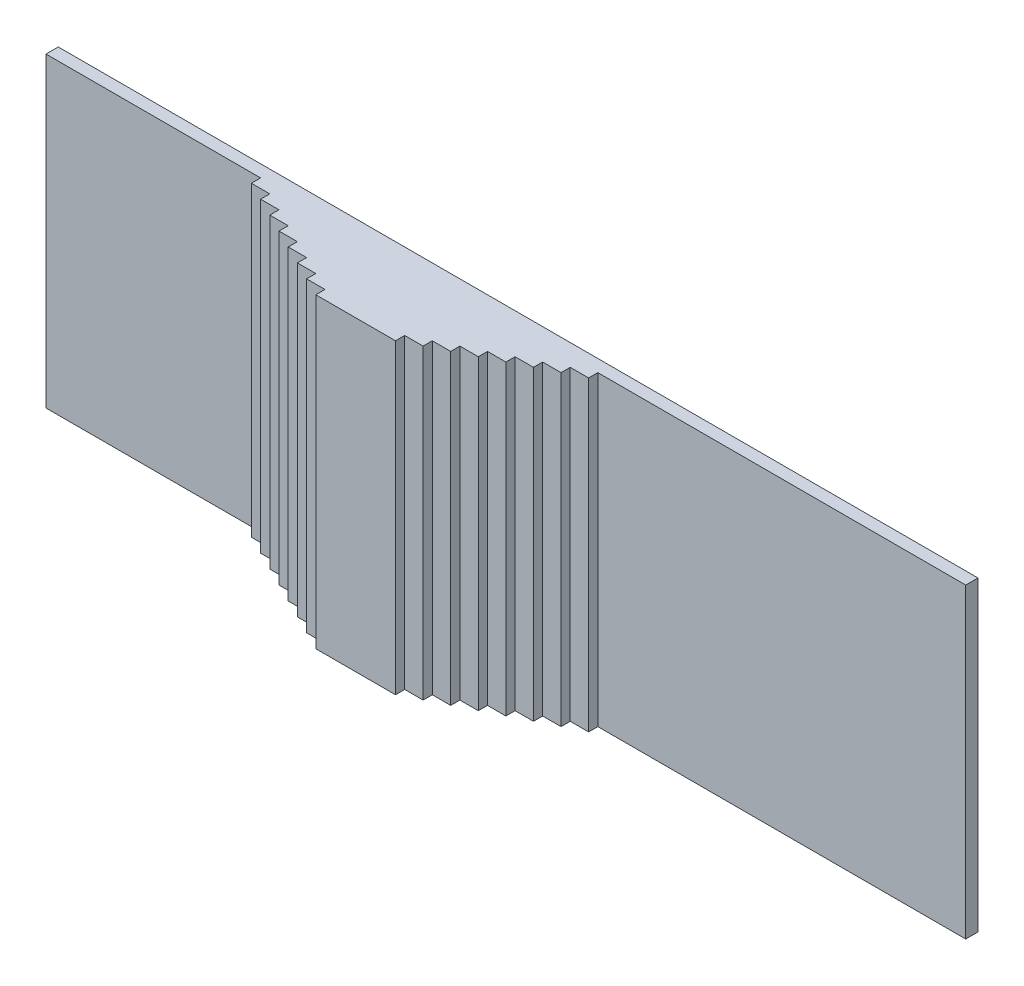
SolidWorks part; units mm, degrees
note: The reader was unsure of these and kept them because the rebuilt part matched: shared geometry of "Sketch4<4>", "Sketch4<5>", "Sketch4<6>", "Sketch4<7>", "Sketch4<8>", "Sketch4<9>", "Sketch4<10>", "Sketch10<3>", "Sketch10<4>", "Sketch10<5>", "Sketch10<6>", "Sketch10<7>", "Sketch10<8>".
ref_plane "Front Plane" through (0, 0, 0) normal (0, 0, 1) x (1, 0, 0)
ref_plane "Top Plane" through (0, 0, 0) normal (0, 1, 0) x (1, 0, 0)
ref_plane "Right Plane" through (0, 0, 0) normal (1, 0, 0) x (0, 0, -1)
sketch "Sketch3" plane through (0, 0, 0) normal (0, 0, 1) x (1, 0, 0)
  line L1 (-2500, 2500) -> (12500, 2500)
  line L2 (-2500, 2500) -> (-2500, -2500)
  line L3 (-2500, -2500) -> (12500, -2500)
  line L4 (12500, 2500) -> (12500, -2500)
  line L5 (-2500, 2500) -> (12500, -2500) construction
  line L6 (-2500, -2500) -> (12500, 2500) construction
  point P0 (5000, 0)
  dimension "D1" = 15000
  dimension "D2" = 5000
  dimension "D3" = 5000
extrude "Boss-Extrude1" add sketch "Sketch3" along normal blind 200
sketch "Sketch4" plane through (0, 0, 200) normal (0, 0, 1) x (1, 0, 0)
  line L0 (-2500, -2500) -> (12500, -2500) construction
  line L1 (1000, -2500) -> (1300, -2500)
  line L2 (1000, -2500) -> (1000, 2500)
  line L3 (1000, 2500) -> (1300, 2500)
  line L4 (1300, -2500) -> (1300, 2500)
  line L5 (12500, 2500) -> (-2500, 2500) construction
  line L6 (1300, -2500) -> (1300, 2500)
  line L7 (1300, -2500) -> (1600, -2500)
  line L8 (1600, -2500) -> (1600, 2500)
  line L9 (1300, 2500) -> (1600, 2500)
  line L10 (1600, -2500) -> (1600, 2500)
  line L11 (1600, -2500) -> (1900, -2500)
  line L12 (1900, -2500) -> (1900, 2500)
  line L13 (1600, 2500) -> (1900, 2500)
  line L14 (1900, -2500) -> (1900, 2500)
  line L15 (1900, -2500) -> (2200, -2500)
  line L16 (2200, -2500) -> (2200, 2500)
  line L17 (1900, 2500) -> (2200, 2500)
  line L18 (2200, -2500) -> (2200, 2500)
  line L19 (2200, -2500) -> (2500, -2500)
  line L20 (2500, -2500) -> (2500, 2500)
  line L21 (2200, 2500) -> (2500, 2500)
  line L22 (2500, -2500) -> (2500, 2500)
  line L23 (2500, -2500) -> (2800, -2500)
  line L24 (2800, -2500) -> (2800, 2500)
  line L25 (2500, 2500) -> (2800, 2500)
  line L26 (2800, -2500) -> (2800, 2500)
  line L27 (2800, -2500) -> (3100, -2500)
  line L28 (3100, -2500) -> (3100, 2500)
  line L29 (2800, 2500) -> (3100, 2500)
  line L30 (3100, -2500) -> (3100, 2500)
  line L31 (3100, -2500) -> (3400, -2500)
  line L32 (3400, -2500) -> (3400, 2500)
  line L33 (3100, 2500) -> (3400, 2500)
  line M6 (12500, 2500) -> (-2500, 2500)
  line M8 (-2500, -2500) -> (12500, -2500)
  dimension "D1" = 1000
  dimension "D2" = 300
  dimension "D3" = 8
extrude "Step1" add sketch "Sketch4" along normal blind 150 contours L4 L2 M8 M6
extrude "Step2" add sketch "Sketch4<4>" along normal blind 300 contours L8 L4 M8 M6
sketch "Sketch4<4>" plane through (0, 0, 200) normal (0, 0, 1) x (1, 0, 0) same geometry as "Sketch4"
extrude "Step3" add sketch "Sketch4<5>" along normal blind 450 contours L12 L8 M8 M6
sketch "Sketch4<5>" plane through (0, 0, 200) normal (0, 0, 1) x (1, 0, 0) same geometry as "Sketch4"
extrude "Step4" add sketch "Sketch4<6>" along normal blind 600 contours L16 L12 M8 M6
sketch "Sketch4<6>" plane through (0, 0, 200) normal (0, 0, 1) x (1, 0, 0) same geometry as "Sketch4"
extrude "Step5" add sketch "Sketch4<7>" along normal blind 750 contours L20 L16 M8 M6
sketch "Sketch4<7>" plane through (0, 0, 200) normal (0, 0, 1) x (1, 0, 0) same geometry as "Sketch4"
extrude "Step6" add sketch "Sketch4<8>" along normal blind 900 contours L24 L20 M8 M6
sketch "Sketch4<8>" plane through (0, 0, 200) normal (0, 0, 1) x (1, 0, 0) same geometry as "Sketch4"
extrude "Step7" add sketch "Sketch4<9>" along normal blind 1050 contours L28 L24 M8 M6
sketch "Sketch4<9>" plane through (0, 0, 200) normal (0, 0, 1) x (1, 0, 0) same geometry as "Sketch4"
extrude "Step8" add sketch "Sketch4<10>" along normal blind 1200 contours L32 L28 M8 M6
sketch "Sketch4<10>" plane through (0, 0, 200) normal (0, 0, 1) x (1, 0, 0) same geometry as "Sketch4"
sketch "Sketch8" plane through (0, 0, 200) normal (0, 0, 1) x (1, 0, 0)
  line L4 (12500, 2500) -> (3400, 2500)
  line L5 (3400, 2500) -> (3400, -2500)
  line L6 (3400, -2500) -> (12500, -2500)
  line L7 (12500, -2500) -> (12500, 2500)
  line L8 (12500, 2500) -> (3400, 2500)
  line L10 (3400, -2500) -> (12500, -2500)
  line L11 (12500, -2500) -> (12500, 2500)
  line L12 (3400, 2500) -> (3400, -2500)
  dimension "D1" = 0
sketch "Sketch9" plane through (0, 0, 200) normal (0, 0, 1) x (1, 0, 0)
  line L0 (4400, -2500) -> (4400, 2500)
  line L4 (12500, 2500) -> (3400, 2500)
  line L5 (3400, 2500) -> (3400, -2500)
  line L6 (3400, -2500) -> (12500, -2500)
  line L7 (12500, -2500) -> (12500, 2500)
  line L8 (12500, 2500) -> (3400, 2500)
  line L9 (3400, 2500) -> (3400, -2500)
  line L10 (3400, -2500) -> (12500, -2500)
  line L11 (12500, -2500) -> (12500, 2500)
  line M6 (12500, 2500) -> (3400, 2500)
  line M7 (3400, 2500) -> (3400, -2500)
  line M8 (3400, -2500) -> (12500, -2500)
  dimension "D2" = 1000
  dimension "D1" = 0
extrude "Boss-Extrude2" add sketch "Sketch9" along normal blind 1200 contours L0 M8 M6 M7
sketch "Sketch10" plane through (0, 0, 200) normal (0, 0, 1) x (1, 0, 0)
  line L0 (4700, -2500) -> (4700, 2500)
  line L1 (4400, -2500) -> (4700, -2500)
  line L2 (4400, -2500) -> (4400, 2500)
  line L3 (4400, 2500) -> (4700, 2500)
  line L4 (12500, 2500) -> (4400, 2500)
  line L5 (4400, 2500) -> (4400, -2500)
  line L6 (4400, -2500) -> (12500, -2500)
  line L7 (12500, -2500) -> (12500, 2500)
  line L8 (12500, 2500) -> (4400, 2500)
  line L9 (4400, 2500) -> (4400, -2500)
  line L10 (4400, -2500) -> (12500, -2500)
  line L11 (12500, -2500) -> (12500, 2500)
  line L12 (4700, -2500) -> (4700, 2500)
  line L13 (4700, -2500) -> (5000, -2500)
  line L14 (5000, -2500) -> (5000, 2500)
  line L15 (4700, 2500) -> (5000, 2500)
  line L16 (5000, -2500) -> (5000, 2500)
  line L17 (5000, -2500) -> (5300, -2500)
  line L18 (5300, -2500) -> (5300, 2500)
  line L19 (5000, 2500) -> (5300, 2500)
  line L20 (5300, -2500) -> (5300, 2500)
  line L21 (5300, -2500) -> (5600, -2500)
  line L22 (5600, -2500) -> (5600, 2500)
  line L23 (5300, 2500) -> (5600, 2500)
  line L24 (5600, -2500) -> (5600, 2500)
  line L25 (5600, -2500) -> (5900, -2500)
  line L26 (5900, -2500) -> (5900, 2500)
  line L27 (5600, 2500) -> (5900, 2500)
  line L28 (5900, -2500) -> (5900, 2500)
  line L29 (5900, -2500) -> (6200, -2500)
  line L30 (6200, -2500) -> (6200, 2500)
  line L31 (5900, 2500) -> (6200, 2500)
  line L32 (6200, -2500) -> (6200, 2500)
  line L33 (6200, -2500) -> (6500, -2500)
  line L34 (6500, -2500) -> (6500, 2500)
  line L35 (6200, 2500) -> (6500, 2500)
  line L36 (6500, -2500) -> (6500, 2500)
  line L37 (6500, -2500) -> (6800, -2500)
  line L38 (6800, -2500) -> (6800, 2500)
  line L39 (6500, 2500) -> (6800, 2500)
  dimension "D2" = 300
  dimension "D1" = 0
  dimension "D3" = 8
extrude "Boss-Extrude3" add sketch "Sketch10" along normal blind 1050 contours L22 L0 L20 L21
extrude "Boss-Extrude4" add sketch "Sketch10<3>" along normal blind 900 contours L22 L14 L8 L0
sketch "Sketch10<3>" plane through (0, 0, 200) normal (0, 0, 1) x (1, 0, 0) same geometry as "Sketch10"
extrude "Boss-Extrude5" add sketch "Sketch10<4>" along normal blind 750 contours L10 L18 L8 L14
sketch "Sketch10<4>" plane through (0, 0, 200) normal (0, 0, 1) x (1, 0, 0) same geometry as "Sketch10"
extrude "Boss-Extrude6" add sketch "Sketch10<5>" along normal blind 600 contours L22 L8 L18
sketch "Sketch10<5>" plane through (0, 0, 200) normal (0, 0, 1) x (1, 0, 0) same geometry as "Sketch10"
extrude "Boss-Extrude7" add sketch "Sketch10<6>" along normal blind 450 contours L10 L26 L8 L22
sketch "Sketch10<6>" plane through (0, 0, 200) normal (0, 0, 1) x (1, 0, 0) same geometry as "Sketch10"
extrude "Boss-Extrude8" add sketch "Sketch10<7>" along normal blind 300 contours L22 L30 L8 L26
sketch "Sketch10<7>" plane through (0, 0, 200) normal (0, 0, 1) x (1, 0, 0) same geometry as "Sketch10"
extrude "Boss-Extrude9" add sketch "Sketch10<8>" along normal blind 150 contours L10 L34 L8 L30
sketch "Sketch10<8>" plane through (0, 0, 200) normal (0, 0, 1) x (1, 0, 0) same geometry as "Sketch10"
